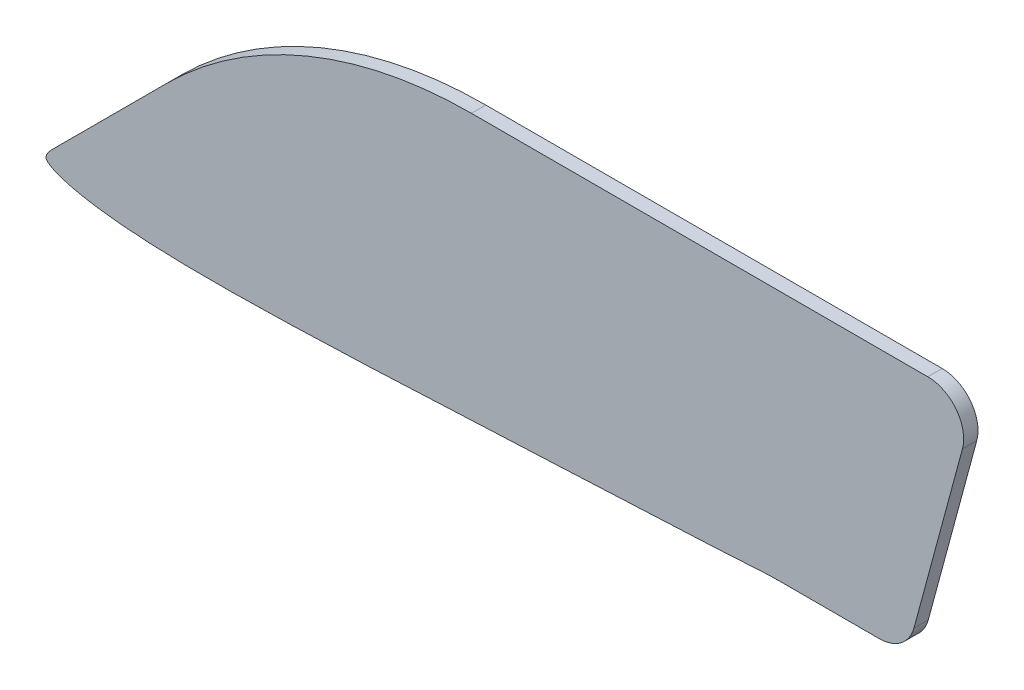
SolidWorks part; units mm, degrees
ref_plane "Front Plane" through (0, 0, 0) normal (0, 0, 1) x (1, 0, 0)
ref_plane "Top Plane" through (0, 0, 0) normal (0, 1, 0) x (1, 0, 0)
ref_plane "Right Plane" through (0, 0, 0) normal (1, 0, 0) x (0, 0, -1)
curve "Curve1"
  spline degree 3 poles (319.3399, -0.0631, 0) (320.1749, 0.0121, 0) (319.2775, -0.0304, 0) (318.5408, -0.0213, 0) (316.7306, 0.0124, 0) (314.5198, 0.1434, 0) (311.6513, 0.3645, 0) (308.3098, 0.7064, 0) (304.5223, 1.1688, 0) (300.3775, 1.7342, 0) (295.943, 2.3803, 0) (291.2893, 3.0786, 0) (286.4795, 3.7953, 0) (281.5654, 4.4835, 0) (276.5911, 5.1112, 0) (271.5953, 5.6552, 0) (266.6171, 6.1013, 0) (261.6991, 6.4472, 0) (256.8868, 6.6894, 0) (252.2271, 6.822, 0) (247.7645, 6.8415, 0) (243.539, 6.7385, 0) (239.586, 6.5122, 0) (235.9364, 6.165, 0) (232.6179, 5.7039, 0) (229.6553, 5.1389, 0) (227.0686, 4.4832, 0) (224.8731, 3.7453, 0) (223.0782, 2.9469, 0) (221.6854, 2.1189, 0) (220.7273, 1.3252, 0) (220.2338, 0.7064, 0) (220.0616, 0.3184, 0) (220.0116, 0.1395, 0) (219.9959, -0.0029, 0) (220.0081, -0.1155, 0) (220.062, -0.2184, 0) (220.1603, -0.338, 0) (220.3145, -0.4779, 0) (220.4826, -0.5989, 0) (220.9421, -0.8937, 0) (221.8924, -1.2976, 0) (223.5205, -1.784, 0) (225.624, -2.2279, 0) (228.1771, -2.6133, 0) (231.1641, -2.9192, 0) (234.5635, -3.137, 0) (238.352, -3.2671, 0) (242.4996, -3.312, 0) (246.9689, -3.2849, 0) (251.716, -3.1932, 0) (256.6914, -3.0476, 0) (261.8415, -2.8575, 0) (267.1088, -2.6383, 0) (272.4315, -2.3988, 0) (277.7457, -2.1515, 0) (282.9865, -1.902, 0) (288.0894, -1.6584, 0) (292.9917, -1.4233, 0) (297.6334, -1.202, 0) (301.9578, -0.9952, 0) (305.9103, -0.8085, 0) (309.4451, -0.64, 0) (312.5051, -0.4927, 0) (315.0892, -0.3596, 0) (317.0641, -0.2502, 0) (318.6672, -0.1355, 0) (319.3399, -0.0631, 0) (320.1749, 0.0121, 0) (319.2775, -0.0304, 0) knots -0.013413 -0.006112 -0.001576 0 0.001644 0.006617 0.014862 0.026171 0.040322 0.057038 0.075955 0.096697 0.118903 0.142213 0.166278 0.190806 0.215581 0.240407 0.265107 0.28948 0.3133 0.336346 0.3584 0.379278 0.398833 0.416933 0.433472 0.448354 0.461506 0.472899 0.482558 0.490505 0.496775 0.500889 0.502032 0.503032 0.503621 0.504144 0.50468 0.505311 0.506426 0.507746 0.50837 0.514497 0.522892 0.533497 0.546244 0.561059 0.577879 0.596602 0.617103 0.639204 0.662686 0.687305 0.712801 0.738887 0.765254 0.791583 0.817549 0.842832 0.867121 0.890118 0.911544 0.931132 0.948636 0.963834 0.976537 0.986587 0.993888 0.998424 1 1.001644 1.006617 1.014862 periodic
sketch "Sketch1" plane through (0, 0, 0) normal (0, 0, 1) x (1, 0, 0)
  line L0 (220.7656, 1.3114) -> (254.4542, 35)
  line L1 (254.4542, 35) -> (349.4542, 35)
  line L2 (349.4542, 35) -> (340.0001, 0)
  line L3 (340.0001, 0) -> (320, 0)
  line L4 (220.0001, 0) -> (220.0001, 27.3876)
  spline S0 degree 3 poles (319.3399, -0.0631) (320.1749, 0.0121) (319.2775, -0.0304) (318.5408, -0.0213) (316.7306, 0.0124) (314.5198, 0.1434) (311.6513, 0.3645) (308.3098, 0.7064) (304.5223, 1.1688) (300.3775, 1.7342) (295.943, 2.3803) (291.2893, 3.0786) (286.4795, 3.7953) (281.5654, 4.4835) (276.5911, 5.1112) (271.5953, 5.6552) (266.6171, 6.1013) (261.6991, 6.4472) (256.8868, 6.6894) (252.2271, 6.822) (247.7645, 6.8415) (243.539, 6.7385) (239.586, 6.5122) (235.9364, 6.165) (232.6179, 5.7039) (229.6553, 5.1389) (227.0686, 4.4832) (224.8731, 3.7453) (223.0782, 2.9469) (221.6854, 2.1189) (220.7273, 1.3252) (220.2338, 0.7064) (220.0616, 0.3184) (220.0116, 0.1395) (219.9959, -0.0029) (220.0081, -0.1155) (220.062, -0.2184) (220.1603, -0.338) (220.3145, -0.4779) (220.4826, -0.5989) (220.9421, -0.8937) (221.8924, -1.2976) (223.5205, -1.784) (225.624, -2.2279) (228.1771, -2.6133) (231.1641, -2.9192) (234.5635, -3.137) (238.352, -3.2671) (242.4996, -3.312) (246.9689, -3.2849) (251.716, -3.1932) (256.6914, -3.0476) (261.8415, -2.8575) (267.1088, -2.6383) (272.4315, -2.3988) (277.7457, -2.1515) (282.9865, -1.902) (288.0894, -1.6584) (292.9917, -1.4233) (297.6334, -1.202) (301.9578, -0.9952) (305.9103, -0.8085) (309.4451, -0.64) (312.5051, -0.4927) (315.0892, -0.3596) (317.0641, -0.2502) (318.6672, -0.1355) (319.3399, -0.0631) (320.1749, 0.0121) (319.2775, -0.0304) knots -0.013413 -0.006112 -0.001576 0 0.001644 0.006617 0.014862 0.026171 0.040322 0.057038 0.075955 0.096697 0.118903 0.142213 0.166278 0.190806 0.215581 0.240407 0.265107 0.28948 0.3133 0.336346 0.3584 0.379278 0.398833 0.416933 0.433472 0.448354 0.461506 0.472899 0.482558 0.490505 0.496775 0.500889 0.502032 0.503032 0.503621 0.504144 0.50468 0.505311 0.506426 0.507746 0.50837 0.514497 0.522892 0.533497 0.546244 0.561059 0.577879 0.596602 0.617103 0.639204 0.662686 0.687305 0.712801 0.738887 0.765254 0.791583 0.817549 0.842832 0.867121 0.890118 0.911544 0.931132 0.948636 0.963834 0.976537 0.986587 0.993888 0.998424 1 1.001644 1.006617 1.014862 only from (320, 0) to (320, 0) construction
  spline S1 degree 3 poles (319.3399, -0.0631) (320.1749, 0.0121) (319.2775, -0.0304) (318.5408, -0.0213) (316.7306, 0.0124) (314.5198, 0.1434) (311.6513, 0.3645) (308.3098, 0.7064) (304.5223, 1.1688) (300.3775, 1.7342) (295.943, 2.3803) (291.2893, 3.0786) (286.4795, 3.7953) (281.5654, 4.4835) (276.5911, 5.1112) (271.5953, 5.6552) (266.6171, 6.1013) (261.6991, 6.4472) (256.8868, 6.6894) (252.2271, 6.822) (247.7645, 6.8415) (243.539, 6.7385) (239.586, 6.5122) (235.9364, 6.165) (232.6179, 5.7039) (229.6553, 5.1389) (227.0686, 4.4832) (224.8731, 3.7453) (223.0782, 2.9469) (221.6854, 2.1189) (220.7273, 1.3252) (220.2338, 0.7064) (220.0616, 0.3184) (220.0116, 0.1395) (219.9959, -0.0029) (220.0081, -0.1155) (220.062, -0.2184) (220.1603, -0.338) (220.3145, -0.4779) (220.4826, -0.5989) (220.9421, -0.8937) (221.8924, -1.2976) (223.5205, -1.784) (225.624, -2.2279) (228.1771, -2.6133) (231.1641, -2.9192) (234.5635, -3.137) (238.352, -3.2671) (242.4996, -3.312) (246.9689, -3.2849) (251.716, -3.1932) (256.6914, -3.0476) (261.8415, -2.8575) (267.1088, -2.6383) (272.4315, -2.3988) (277.7457, -2.1515) (282.9865, -1.902) (288.0894, -1.6584) (292.9917, -1.4233) (297.6334, -1.202) (301.9578, -0.9952) (305.9103, -0.8085) (309.4451, -0.64) (312.5051, -0.4927) (315.0892, -0.3596) (317.0641, -0.2502) (318.6672, -0.1355) (319.3399, -0.0631) (320.1749, 0.0121) (319.2775, -0.0304) knots -0.013413 -0.006112 -0.001576 0 0.001644 0.006617 0.014862 0.026171 0.040322 0.057038 0.075955 0.096697 0.118903 0.142213 0.166278 0.190806 0.215581 0.240407 0.265107 0.28948 0.3133 0.336346 0.3584 0.379278 0.398833 0.416933 0.433472 0.448354 0.461506 0.472899 0.482558 0.490505 0.496775 0.500889 0.502032 0.503032 0.503621 0.504144 0.50468 0.505311 0.506426 0.507746 0.50837 0.514497 0.522892 0.533497 0.546244 0.561059 0.577879 0.596602 0.617103 0.639204 0.662686 0.687305 0.712801 0.738887 0.765254 0.791583 0.817549 0.842832 0.867121 0.890118 0.911544 0.931132 0.948636 0.963834 0.976537 0.986587 0.993888 0.998424 1 1.001644 1.006617 1.014862 only from (320, 0) to (320, 0)
  dimension "D1" = 135
  dimension "D2" = 35
  dimension "D3" = 120
  dimension "D4" = 95
extrude "Boss-Extrude1" add sketch "Sketch1" along normal blind 2 contours S1 L3 L2 L1 L0 | S1 region at (294.3787, 18.5822, 0) region at (259.0168, 1.412, 0)
fillet "Fillet1" radius 60 2 edges at (320, 0, 1) (254.4542, 35, 1)
fillet "Fillet2" radius 5 2 edges at (349.4542, 35, 1) (340.0001, 0, 1)
